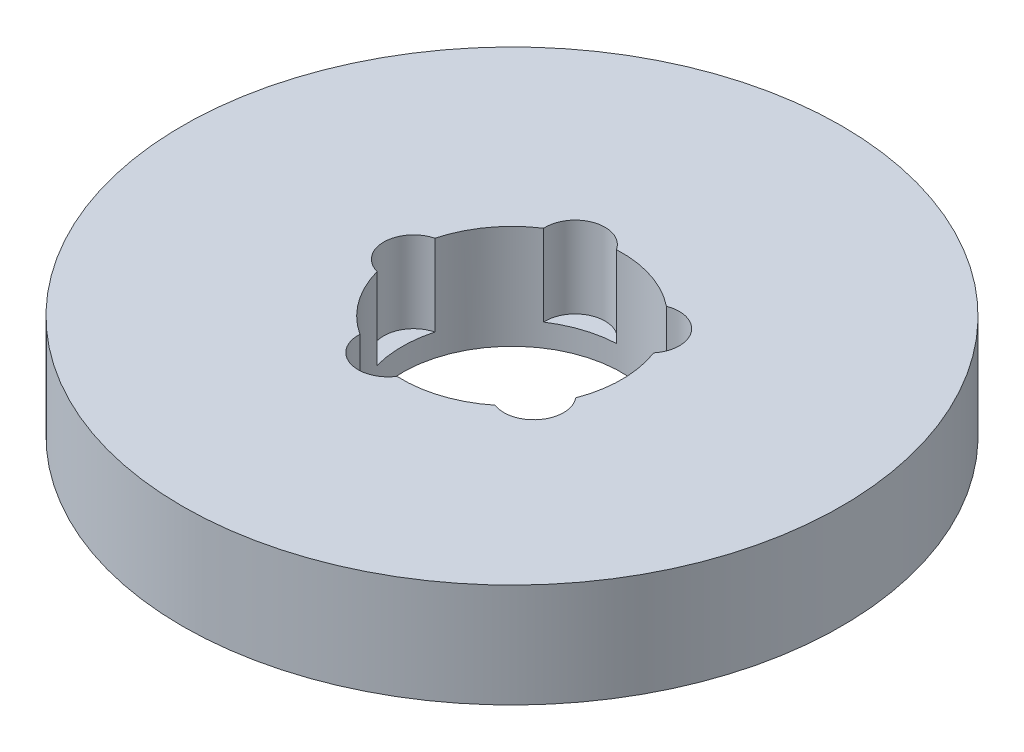
SolidWorks part; units mm, degrees
ref_plane "Front Plane" through (0, 0, 0) normal (0, 0, 1) x (1, 0, 0)
ref_plane "Top Plane" through (0, 0, 0) normal (0, 1, 0) x (1, 0, 0)
ref_plane "Right Plane" through (0, 0, 0) normal (1, 0, 0) x (0, 0, -1)
sketch "Sketch1" plane through (0, 0, 0) normal (0, 1, 0) x (1, 0, 0)
  circle A0 centre (0, 0) radius 82.5
  dimension "FLANGE_OD" = 165
extrude "Boss-Extrude1" add sketch "Sketch1" along normal blind 26
sketch "Sketch2" plane through (0, 0, 0) normal (0, 1, 0) x (1, 0, 0)
  circle A0 centre (0, 0) radius 27.5
  dimension "BORE_D" = 55
extrude "Cut-Extrude1" cut sketch "Sketch2" along normal through all
sketch "Sketch3" plane through (0, 26, 0) normal (0, 1, 0) x (1, 0, 0)
  circle A0 centre (0, 0) radius 24.6345 construction
  circle A1 centre (-24.6345, 0) radius 7.4745
  dimension "BOLT_D" = 14.9491
  dimension "BOLT_PCD" = 49.269
extrude "Cut-Extrude2" cut sketch "Sketch3" against normal blind 20.3468
pattern_circular "CirPattern1" count 5 over 360 about axis through (0, 0, 0) along (0, 1, 0) of "Cut-Extrude2"
